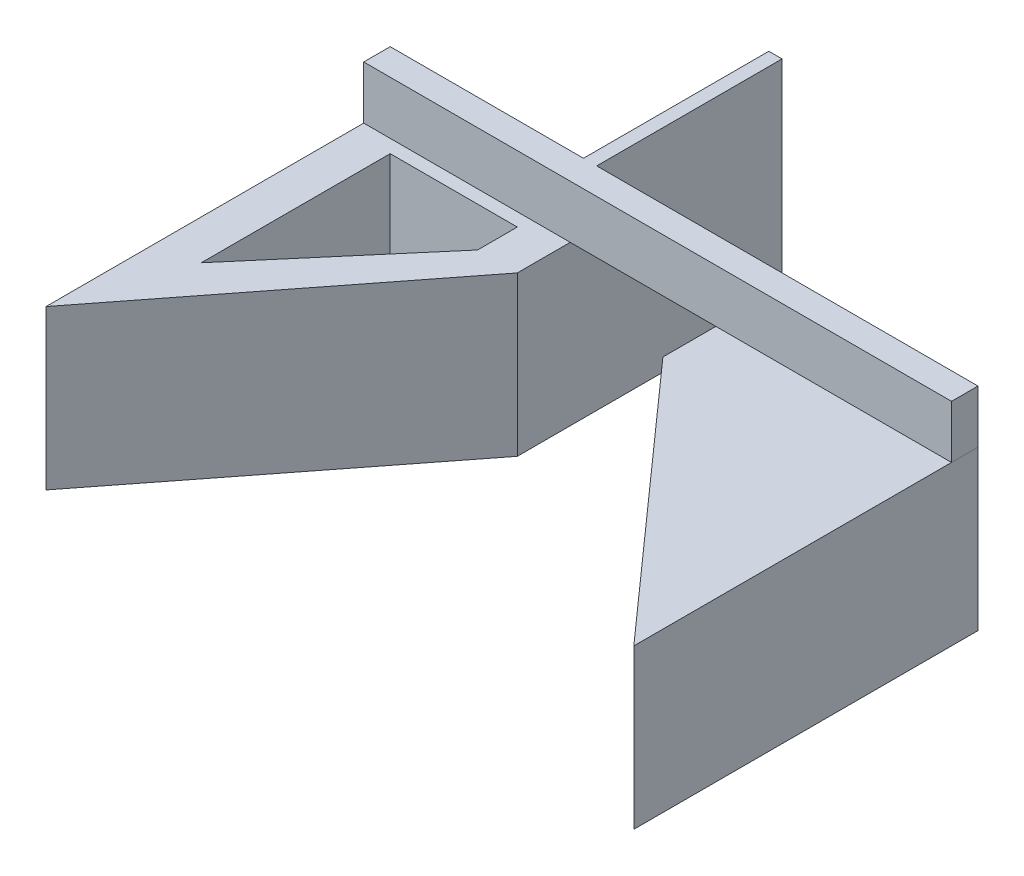
SolidWorks part; units mm, degrees
ref_plane "Front Plane" through (0, 0, 0) normal (0, 0, 1) x (1, 0, 0)
ref_plane "Top Plane" through (0, 0, 0) normal (0, 1, 0) x (1, 0, 0)
ref_plane "Right Plane" through (0, 0, 0) normal (1, 0, 0) x (0, 0, -1)
sketch "Sketch1" plane through (0, 0, 0) normal (0, 1, 0) x (1, 0, 0)
  line L0 (0, 42.7008) -> (0, 27.7008)
  line L1 (0, 42.7008) -> (89, 42.7008)
  line L2 (0, 0) -> (-49.1968, 0) construction
  line L3 (-49.1968, 0) -> (52.6104, 0) construction
  line L4 (-133, 12.7008) -> (-133, -87.2992)
  line L5 (-133, -87.2992) -> (-55, 12.7008)
  line L13 (-133, 42.7008) -> (-55, 42.7008)
  line L14 (-55, 12.7008) -> (-55, 42.7008)
  line L20 (-133, 42.7008) -> (-133, 12.7008)
  line L26 (-118, 27.7008) -> (-118, -43.6794)
  line L27 (-118, -43.6794) -> (-70, 12.7008)
  line L28 (-70, 12.7008) -> (-70, 27.7008)
  line L29 (-70, 27.7008) -> (-118, 27.7008)
  line L39 (89, 42.7008) -> (89, -87.2992)
  line L40 (89, -87.2992) -> (0, 12.7008)
  line L41 (0, 12.7008) -> (0, 27.7008)
  dimension "D1" = 55
  dimension "D2" = 78
  dimension "D3" = 100
  dimension "D4" = 30
  dimension "D5" = 15
  dimension "D6" = 15
  dimension "D7" = 15
  dimension "D8" = 15
  dimension "D9" = 89
extrude "Boss-Extrude1" add sketch "Sketch1" along normal blind 60
sketch "Sketch3" plane through (0, 60, 0) normal (0, 1, 0) x (1, 0, 0)
  line L13 (-133, 42.7008) -> (-133, -87.2992) construction
  line L14 (89, 42.7008) -> (-133, 42.7008)
  line L15 (89, 42.7008) -> (89, 32.7008)
  line L16 (89, 32.7008) -> (-133, 32.7008)
  line L17 (-133, 42.7008) -> (-133, 32.7008)
  dimension "D1" = 10
extrude "Boss-Extrude3" add sketch "Sketch3" along normal blind 20
ref_plane "Plane1" through (0, 0, 0) normal (0, -1, 0) x (-1, 0, 0)
sketch "Sketch4" plane through (0, 0, 0) normal (0, -1, 0) x (-1, 0, 0)
  line L1 (55, 42.7008) -> (60, 42.7008)
  line L2 (55, 42.7008) -> (55, 112.7008)
  line L3 (55, 112.7008) -> (60, 112.7008)
  line L4 (60, 42.7008) -> (60, 112.7008)
  dimension "D1" = 70
  dimension "D2" = 5
extrude "Boss-Extrude4" add sketch "Sketch4" against normal up to vertex (80 mm away) up to point (89, 80, -42.7008)
